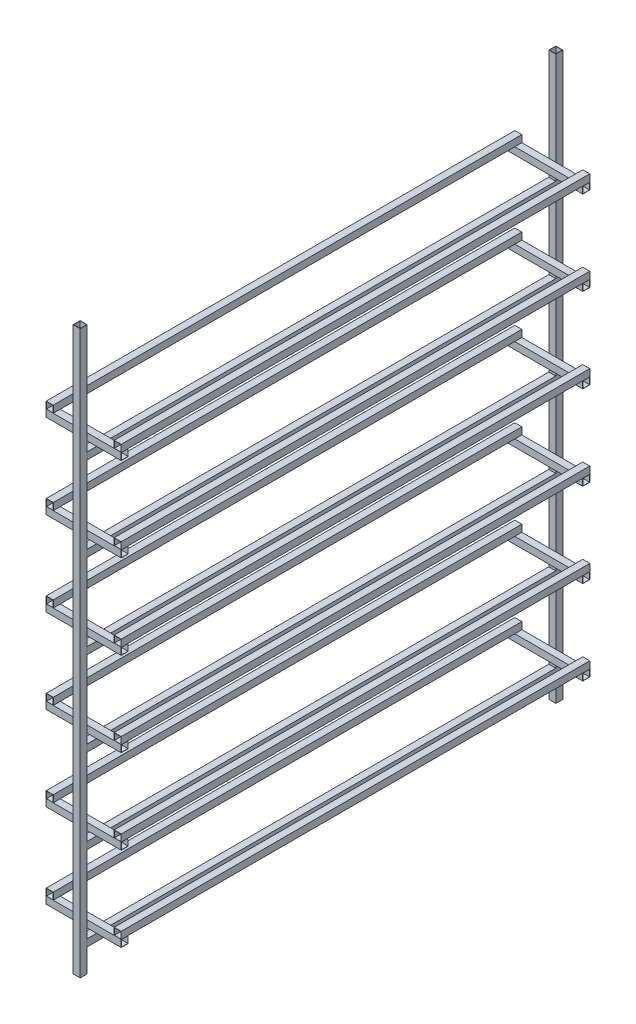
SolidWorks part; units mm, degrees
ref_plane "Alzado" through (0, 0, 0) normal (0, 0, 1) x (1, 0, 0)
ref_plane "Planta" through (0, 0, 0) normal (0, 1, 0) x (1, 0, 0)
ref_plane "Vista lateral" through (0, 0, 0) normal (1, 0, 0) x (0, 0, -1)
sketch "Croquis1" plane through (0, 0, 0) normal (0, 1, 0) x (1, 0, 0)
  line L1 (15, -15) -> (-15, -15)
  line L2 (15, -15) -> (15, 15)
  line L3 (15, 15) -> (-15, 15)
  line L4 (-15, -15) -> (-15, 15)
  line L5 (15, -15) -> (-15, 15) construction
  line L6 (15, 15) -> (-15, -15) construction
  circle A0 centre (0, 0) radius 21.2132 construction
  point P0 (0, 0)
  dimension "D1" = 30
extrude "Extruir-Lámina1" add sketch "Croquis1" along normal blind 2400 thin thin type one direction reverse wall 1
sketch "Croquis2" plane through (0, 0, -15) normal (0, 0, -1) x (-1, 0, 0)
  line L0 (-15, 2400) -> (-15, 0) construction
  line L1 (-15, 100) -> (15, 100)
  line L2 (-15, 100) -> (-15, 130)
  line L3 (-15, 130) -> (15, 130)
  line L4 (15, 100) -> (15, 130)
  line L5 (15, 2400) -> (15, 0) construction
  line L6 (-15, 0) -> (15, 0) construction
  dimension "D1" = 100
extrude "Extruir-Lámina2" add sketch "Croquis2" along normal blind 2000 separate body thin thin type one direction reverse wall 1
pattern_linear "MatrizL6" count 6 spacing 360 along (0, 1, 0) of bodies 103
sketch "Croquis3" plane through (0, 0, 0) normal (0, 1, 0) x (1, 0, 0)
  line L0 (15, 2015) -> (-15, 2045) construction
  line L1 (-15, 2015) -> (15, 2015)
  line L2 (-15, 2015) -> (-15, 2045)
  line L3 (-15, 2045) -> (15, 2045)
  line L4 (15, 2015) -> (15, 2045)
  circle A0 centre (0, 2030) radius 21.2132 construction
extrude "Extruir-Lámina3" add sketch "Croquis3" along normal up to surface (2400 mm away) thin up to face at (0, 2400, 0) thin type one direction reverse wall 1
sketch "Croquis6" plane through (0, 0, 0) normal (1, 0, 0) x (0, 0, -1)
  line L0 (-15, 0) -> (15, 0) construction
  line L1 (15, 170) -> (45, 170)
  line L2 (15, 170) -> (15, 200)
  line L3 (15, 200) -> (45, 200)
  line L4 (45, 170) -> (45, 200)
  line L5 (15, 2400) -> (15, 0) construction
  line L6 (2015, 130) -> (15, 130) construction
  line L7 (1015, 130) -> (1015, 460) construction
  line L8 (2015, 460) -> (15, 460) construction
  line L9 (1985, 170) -> (1985, 200)
  line L10 (2015, 200) -> (1985, 200)
  line L11 (2015, 170) -> (2015, 200)
  line L12 (2015, 170) -> (1985, 170)
  dimension "D1" = 40
extrude "Extruir-Lámina4" add sketch "Croquis6" along normal mid plane 320 separate body thin thin type one direction reverse wall 1
pattern_linear "MatrizL7" count 6 spacing 360 along (0, 1, 0) of bodies 110
pattern_linear "MatrizL8" count 6 spacing 360 along (0, 1, 0) of bodies 116
sketch "Croquis7" plane through (0, 0, -15) normal (0, 0, 1) x (1, 0, 0)
  line L0 (0, 0) -> (0, 2400) construction
  line L1 (160, 200) -> (130, 200)
  line L2 (160, 200) -> (160, 230)
  line L3 (160, 230) -> (130, 230)
  line L4 (130, 200) -> (130, 230)
  line L5 (-15, 2400) -> (15, 2400) construction
  line L6 (-130, 200) -> (-130, 230)
  line L7 (-160, 230) -> (-130, 230)
  line L8 (-160, 200) -> (-160, 230)
  line L9 (-160, 200) -> (-130, 200)
  dimension "D1" = 30
extrude "Extruir-Lámina5" add sketch "Croquis7" against normal up to surface (2000 mm away) separate body thin up to face at (0, 185, -2015) thin type one direction reverse wall 1
pattern_linear "MatrizL9" count 6 spacing 360 along (0, 1, 0) of bodies 123 122
